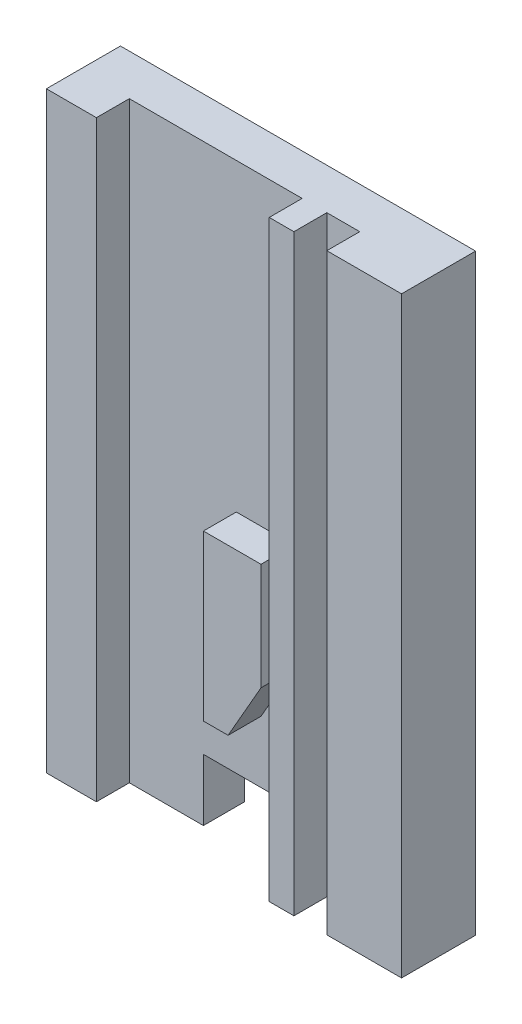
SolidWorks part; units mm, degrees
ref_plane "Front Plane" through (0, 0, 0) normal (0, 0, 1) x (1, 0, 0)
ref_plane "Top Plane" through (0, 0, 0) normal (0, 1, 0) x (1, 0, 0)
ref_plane "Right Plane" through (0, 0, 0) normal (1, 0, 0) x (0, 0, -1)
ref_plane "Plane1" through (0, 0, 0) normal (0, 0, -1) x (-1, 0, 0)
sketch "Sketch1" plane through (0, 0, 0) normal (0, 0, -1) x (-1, 0, 0)
  line L0 (-21.58, 36) -> (-21.58, -36)
  line L1 (-21.58, -36) -> (21.58, -36)
  line L2 (21.58, -36) -> (21.58, 36)
  line L3 (21.58, 36) -> (-21.58, 36)
extrude "Boss-Extrude1" add sketch "Sketch1" against normal blind 9
sketch "Sketch2" plane through (0, 36, 0) normal (0, 1, 0) x (-1, 0, 0)
  line L0 (15.5, 5) -> (15.5, 9)
  line L1 (15.5, 9) -> (-21.58, 9)
  line L2 (-21.58, 9) -> (-21.58, 5)
  line L3 (-21.58, 5) -> (15.5, 5)
extrude "Cut-Extrude1" cut sketch "Sketch2" against normal through all
sketch "Sketch3" plane through (0, 0, 5) normal (0, 0, 1) x (1, 0, 0)
  line L0 (21.58, -36) -> (21.58, -28.5)
  line L1 (21.58, -28.5) -> (-6.5, -28.5)
  line L2 (-6.5, -28.5) -> (-6.5, -36)
  line L3 (-6.5, -36) -> (21.58, -36)
extrude "Cut-Extrude2" cut sketch "Sketch3" against normal through all
sketch "Sketch4" plane through (0, 0, 5) normal (0, 0, 1) x (1, 0, 0)
  line L0 (5.5, -28.5) -> (5.5, 36)
  line L1 (5.5, 36) -> (21.58, 36)
  line L2 (21.58, 36) -> (21.58, -28.5)
  line L3 (21.58, -28.5) -> (5.5, -28.5)
extrude "Boss-Extrude2" add sketch "Sketch4" along normal blind 4
sketch "Sketch5" plane through (0, -28.5, 0) normal (0, -1, 0) x (1, 0, 0)
  line L0 (21.58, 9) -> (21.58, 0)
  line L1 (21.58, 0) -> (5.5, 0)
  line L2 (5.5, 0) -> (5.5, 9)
  line L3 (5.5, 9) -> (21.58, 9)
extrude "Boss-Extrude3" add sketch "Sketch5" along normal blind 7.5
sketch "Sketch6" plane through (0, 36, 0) normal (0, 1, 0) x (-1, 0, 0)
  line L0 (-8.5, 9) -> (-12.5, 9)
  line L1 (-12.5, 9) -> (-12.5, 5)
  line L2 (-12.5, 5) -> (-8.5, 5)
  line L3 (-8.5, 5) -> (-8.5, 9)
extrude "Cut-Extrude3" cut sketch "Sketch6" against normal through all
sketch "Sketch7" plane through (0, 0, 5) normal (0, 0, 1) x (1, 0, 0)
  line L0 (-2.5, -1) -> (4.5, -1)
  line L1 (4.5, -1) -> (4.5, -14)
  line L2 (4.5, -14) -> (0.5, -21)
  line L3 (0.5, -21) -> (-2.5, -21)
  line L4 (-2.5, -21) -> (-2.5, -1)
extrude "Boss-Extrude4" add sketch "Sketch7" along normal blind 4
